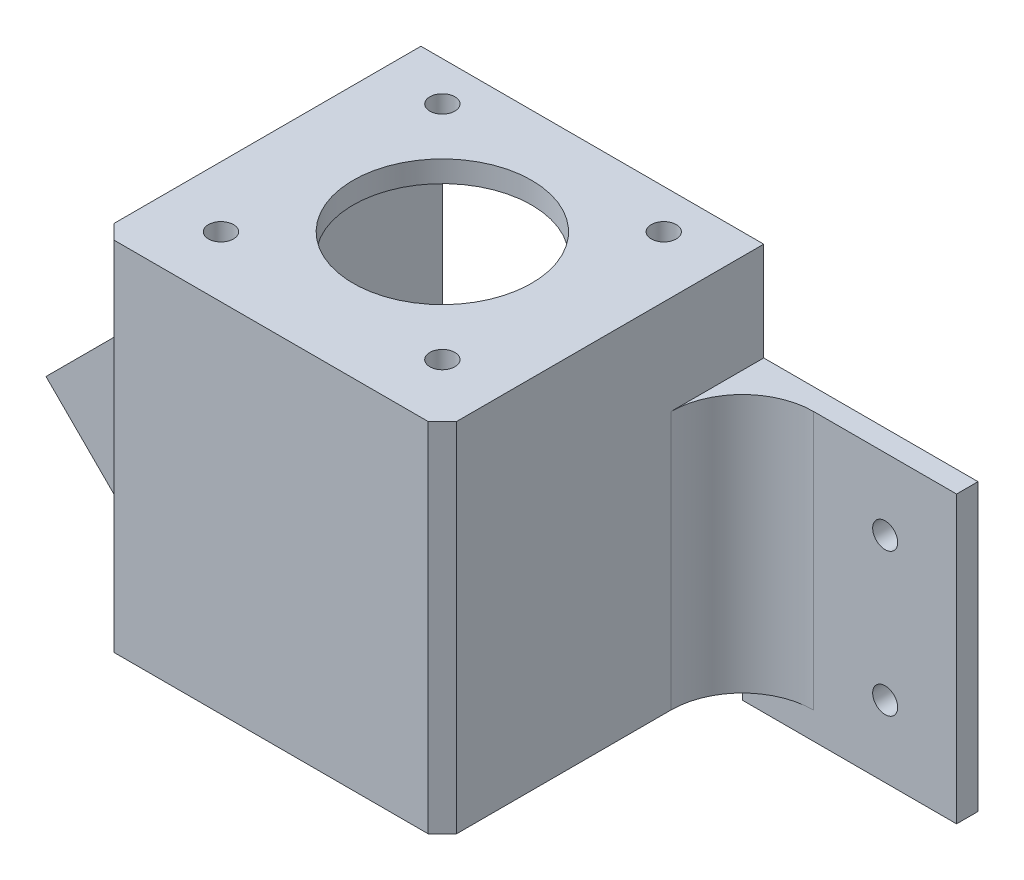
SolidWorks part; units mm, degrees
ref_plane "Front Plane" through (0, 0, 0) normal (0, 0, 1) x (1, 0, 0)
ref_plane "Top Plane" through (0, 0, 0) normal (0, 1, 0) x (1, 0, 0)
ref_plane "Right Plane" through (0, 0, 0) normal (1, 0, 0) x (0, 0, -1)
sketch "Sketch1" plane through (0, 0, 0) normal (0, 1, 0) x (1, 0, 0)
  line L0 (-24, 21) -> (-24, -24)
  line L1 (-21, 21) -> (21, 21) construction
  line L2 (-21, 21) -> (-21, -21) construction
  line L3 (-21, -21) -> (21, -21) construction
  line L4 (21, 21) -> (21, -21) construction
  line L5 (-21, 21) -> (21, -21) construction
  line L6 (-21, -21) -> (21, 21) construction
  line L7 (-24, -24) -> (24, -24)
  line L8 (24, 21) -> (24, -24)
  line L9 (-24, 21) -> (24, 21)
  point P0 (0, 0)
  dimension "D1" = 42
  dimension "D2" = 3
extrude "Boss-Extrude1" add sketch "Sketch1" along normal blind 3
sketch "Sketch2" plane through (0, 0, 0) normal (0, -1, 0) x (1, 0, 0)
  line L1 (-21, 21) -> (21, 21)
  line L2 (-21, 21) -> (-21, -21)
  line L4 (21, 21) -> (21, -21)
  line L5 (-21, 21) -> (21, -21) construction
  line L6 (-21, -21) -> (21, 21) construction
  line L7 (24, -21) -> (-24, -21) construction
  line L8 (21, -21) -> (24, -21)
  line L9 (-24, 24) -> (24, 24)
  line L10 (-24, 24) -> (-24, -21)
  line L11 (-24, -21) -> (-21, -21)
  line L12 (24, 24) -> (24, -21)
  point P0 (0, 0)
  dimension "D1" = 42
extrude "Boss-Extrude2" add sketch "Sketch2" along normal blind 47
sketch "Sketch3" plane through (24, 0, 0) normal (1, 0, 0) x (0, 0, -1)
  line L1 (21, -10.8) -> (18, -10.8)
  line L2 (21, -10.8) -> (21, -50.8)
  line L3 (21, -50.8) -> (18, -50.8)
  line L4 (18, -10.8) -> (18, -50.8)
  line L5 (21, 3) -> (21, -47) construction
  line L6 (-24, 3) -> (21, 3) construction
  dimension "D1" = 3
  dimension "D2" = 40
  dimension "D3" = 13.8
extrude "Boss-Extrude3" add sketch "Sketch3" along normal blind 30
sketch "Sketch4" plane through (0, 0, -21) normal (0, 0, -1) x (-1, 0, 0)
  line L0 (24, -10.8) -> (73.4975, -60.2975)
  line L1 (73.4975, -60.2975) -> (45.2132, -88.5817)
  line L2 (45.2132, -88.5817) -> (24, -67.3685)
  line L3 (24, 3) -> (24, -47) construction
  line L4 (24, -10.8) -> (24, -67.3685)
  dimension "D1" = 45
  dimension "D2" = 30
  dimension "D3" = 40
extrude "Boss-Extrude4" add sketch "Sketch4" against normal blind 3
fillet "Fillet1" radius 10 2 edges at (-24, -28.9, -18) (24, -28.9, -18)
chamfer "Chamfer1" distance 2 angle 45 2 edges at (-24, -22, 24) (24, -22, 24)
sketch "Sketch5" plane through (0, 0, 0) normal (0, -1, 0) x (1, 0, 0)
  line L7 (-15.5, 15.5) -> (15.5, 15.5) construction
  line L8 (-15.5, 15.5) -> (-15.5, -15.5) construction
  line L9 (-15.5, -15.5) -> (15.5, -15.5) construction
  line L10 (15.5, 15.5) -> (15.5, -15.5) construction
  line L11 (-15.5, 15.5) -> (15.5, -15.5) construction
  line L12 (-15.5, -15.5) -> (15.5, 15.5) construction
  circle A0 centre (-15.5, 15.5) radius 1.75
  circle A1 centre (15.5, 15.5) radius 1.75
  circle A2 centre (15.5, -15.5) radius 1.75
  circle A3 centre (-15.5, -15.5) radius 1.75
  circle A4 centre (0, 0) radius 12.5
  point P0 (0, 0)
  dimension "D2" = 4
  dimension "D3" = 3.5
  dimension "D4" = 25
  dimension "D1" = 31
extrude "Cut-Extrude1" cut sketch "Sketch5" against normal through all
ref_plane "Plane1" through (0, -37, 0) normal (0, -1, 0) x (-1, 0, 0)
sketch "Sketch6" plane through (0, -37, 0) normal (0, -1, 0) x (-1, 0, 0)
  line L0 (24, 3.8579) -> (38.1421, 18)
  line L2 (73.4975, 18) -> (34, 18) construction
  line L3 (24, -22) -> (24, 8) construction
  line L4 (24, 18) -> (45.2132, 18) construction
  dimension "D1" = 45
  dimension "D2" = 20
sketch "Sketch7" plane through (0, 0, -18) normal (0, 0, 1) x (1, 0, 0)
  line L0 (44, -10.8) -> (44, -50.8) construction
  line L1 (54, -10.8) -> (34, -10.8) construction
  line L2 (54, -50.8) -> (24, -50.8) construction
  line L3 (-53.7487, -40.5487) -> (-25.4645, -68.833) construction
  line L4 (-73.4975, -60.2975) -> (-34, -20.8) construction
  line L5 (54, -50.8) -> (24, -50.8) construction
  line L6 (-45.2132, -88.5817) -> (-73.4975, -60.2975) construction
  line L7 (-53.7487, -40.5487) -> (-73.4975, -60.2975) construction
  line L8 (-63.6231, -50.4231) -> (-35.3388, -78.7074) construction
  line L9 (-24, -67.3685) -> (-45.2132, -88.5817) construction
  line L10 (-24, -67.3685) -> (-45.2132, -88.5817) construction
  circle A0 centre (44, -20.8) radius 1.75
  circle A1 centre (44, -40.8) radius 1.75
  circle A2 centre (-56.552, -57.4942) radius 1.75
  circle A3 centre (-42.4099, -71.6363) radius 1.75
  dimension "D1" = 10
  dimension "D3" = 3.5
  dimension "D4" = 3.5
  dimension "D5" = 3.5
  dimension "D7" = 3.5
  dimension "D2" = 10
  dimension "D6" = 10
  dimension "D8" = 10
extrude "Cut-Extrude2" cut sketch "Sketch7" against normal through all
